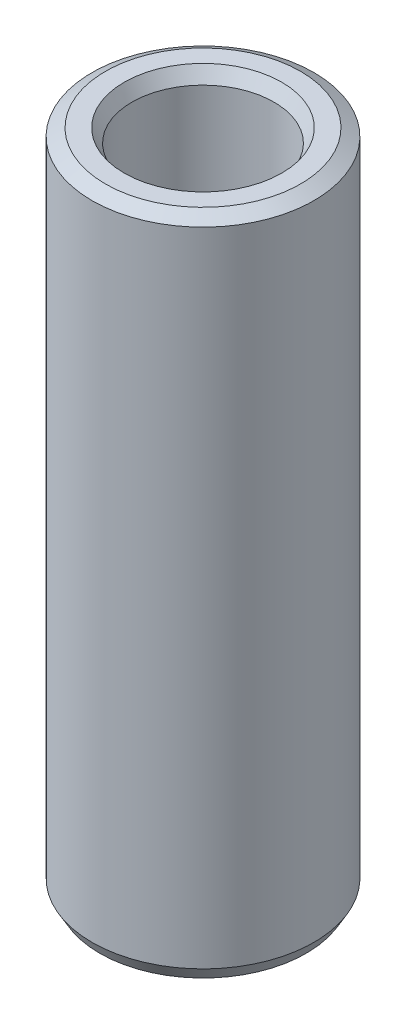
SolidWorks part; units mm, degrees
ref_plane "Front Plane" through (0, 0, 0) normal (0, 0, 1) x (1, 0, 0)
ref_plane "Top Plane" through (0, 0, 0) normal (0, 1, 0) x (1, 0, 0)
ref_plane "Right Plane" through (0, 0, 0) normal (1, 0, 0) x (0, 0, -1)
sketch "Sketch1" plane through (0, 0, 0) normal (0, 1, 0) x (1, 0, 0)
  circle A0 centre (0, 0) radius 42.5
  dimension "SLEEVE_OD" = 85
extrude "Boss-Extrude1" add sketch "Sketch1" along normal blind 254.1131
sketch "Sketch2" plane through (0, 0, 0) normal (0, 1, 0) x (1, 0, 0)
  circle A0 centre (0, 0) radius 27.2115
  dimension "BORE_D" = 54.4231
extrude "Cut-Extrude1" cut sketch "Sketch2" along normal through all
chamfer "Chamfer1" distance 2.9584 angle 60 4 edges at (0, 254.1131, 27.2115) (0, 0, 27.2115) (0, 0, 42.5) (0, 254.1131, 42.5) first distance on face at (0, 254.1131, 27.2115) first distance on face at (0, 0, 27.2115) first distance on face at (0, 254.1131, 42.5)
